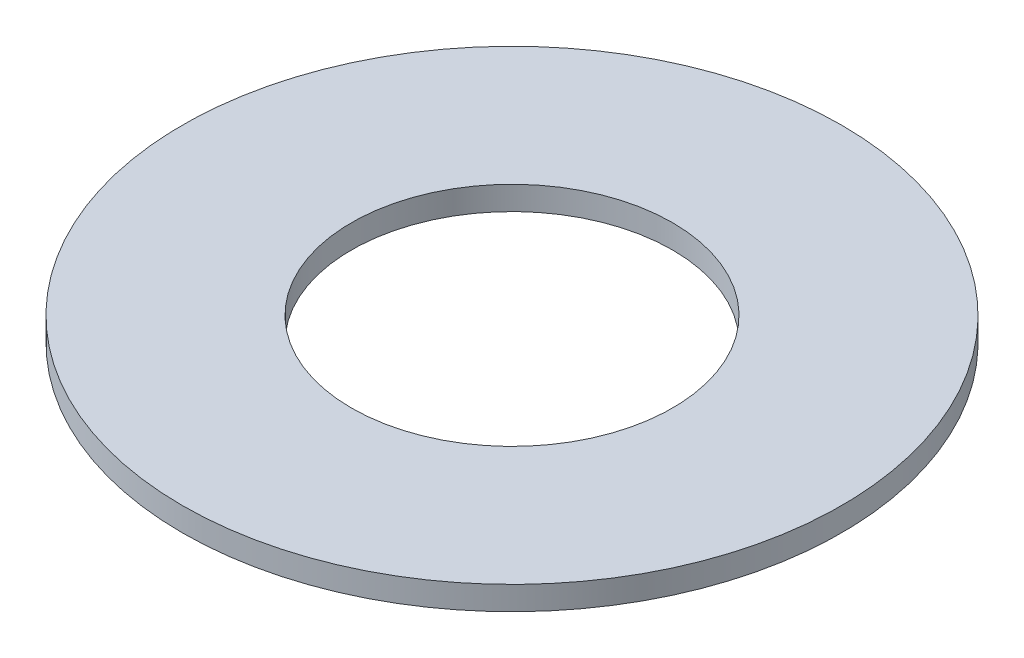
SolidWorks part; units mm, degrees
ref_plane "Front Plane" through (0, 0, 0) normal (0, 0, 1) x (1, 0, 0)
ref_plane "Top Plane" through (0, 0, 0) normal (0, 1, 0) x (1, 0, 0)
ref_plane "Right Plane" through (0, 0, 0) normal (1, 0, 0) x (0, 0, -1)
sketch "Sketch1" plane through (0, 0, 0) normal (0, 1, 0) x (1, 0, 0)
  circle A0 centre (0, 0) radius 97.5
  dimension "FLANGE_OD" = 195
extrude "Boss-Extrude1" add sketch "Sketch1" along normal blind 7
sketch "Sketch2" plane through (0, 0, 0) normal (0, 1, 0) x (1, 0, 0)
  circle A0 centre (0, 0) radius 47.5
  dimension "BORE_D" = 95
extrude "Cut-Extrude1" cut sketch "Sketch2" along normal through all
sketch "Sketch3" plane through (0, 7, 0) normal (0, 1, 0) x (1, 0, 0)
  circle A0 centre (0, 0) radius 38.3728 construction
  circle A1 centre (-38.3728, 0) radius 8.463
  dimension "BOLT_D" = 16.926
  dimension "BOLT_PCD" = 76.7456
extrude "Cut-Extrude2" cut sketch "Sketch3" against normal blind 5.7121 rebuild error yes
pattern_circular "CirPattern1" count 4 over 360 rebuild error yes
